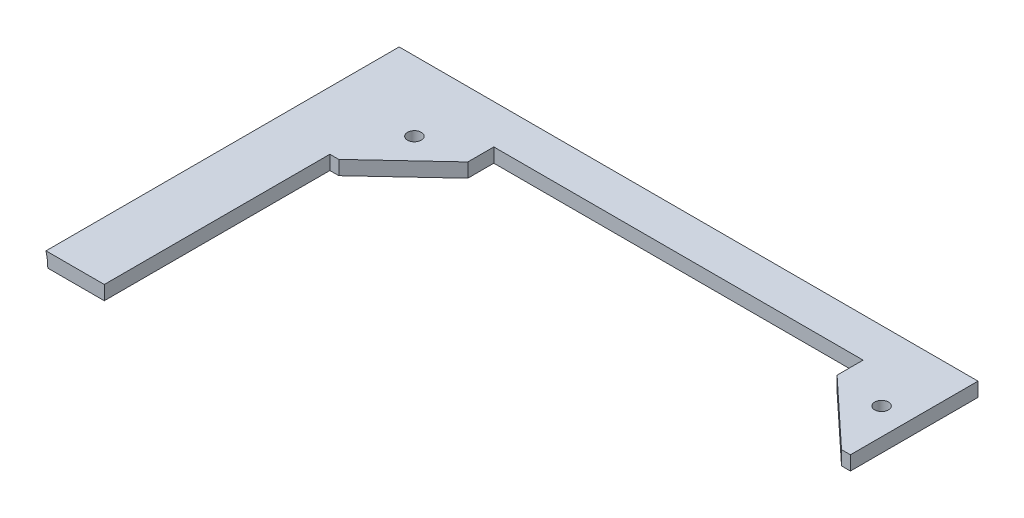
SolidWorks part; units mm, degrees
material "AISI 4130 Steel, annealed at 865C"
ref_plane "X-Y Datum" through (0, 0, 0) normal (0, 0, 1) x (1, 0, 0)
ref_plane "X-Z Datum" through (0, 0, 0) normal (0, 1, 0) x (1, 0, 0)
ref_plane "Y-Z Datum" through (0, 0, 0) normal (1, 0, 0) x (0, 0, -1)
sketch "Sketch1" plane through (0, 0, 0) normal (0, 1, 0) x (1, 0, 0)
  line L1 (-76.2, -38.1) -> (76.2, -38.1)
  line L2 (-76.2, -38.1) -> (-76.2, 38.1)
  line L3 (-76.2, 38.1) -> (76.2, 38.1)
  line L4 (76.2, -38.1) -> (76.2, 38.1)
  line L5 (-76.2, -38.1) -> (76.2, 38.1) construction
  line L6 (-76.2, 38.1) -> (76.2, -38.1) construction
  point P0 (0, 0)
  dimension "D1" = 152.4
  dimension "D2" = 76.2
extrude "Boss-Extrude1" add sketch "Sketch1" along normal blind 3.175 contours L3 L4 L1 L2
sketch "Sketch2" plane through (0, 3.175, 0) normal (0, 1, 0) x (1, 0, 0)
  line L0 (-56.5, 12.6) -> (-41.5, 26.6) construction
  line L1 (-41.5, 26.6) -> (-41.5, 32.45) construction
  line L2 (-41.5, 32.45) -> (41.5, 32.45) construction
  line L3 (41.5, 32.45) -> (41.5, 26.6) construction
  line L4 (-76.2, 38.1) -> (-76.2, -38.1)
  line L5 (-76.2, -38.1) -> (76.2, -38.1)
  line L6 (76.2, -38.1) -> (76.2, 38.1)
  line L7 (76.2, 38.1) -> (-76.2, 38.1)
  line L8 (-76.2, 38.1) -> (-76.2, -38.1)
  line L9 (-76.2, -38.1) -> (76.2, -38.1)
  line L10 (76.2, -38.1) -> (76.2, 38.1)
  line L11 (76.2, 38.1) -> (-76.2, 38.1)
  line L12 (41.5, 26.6) -> (56.5, 12.6) construction
  line L13 (-56.5, 12.6) -> (-41.5, 26.6)
  line L14 (-41.5, 26.6) -> (-41.5, 32.45)
  line L15 (-41.5, 32.45) -> (41.5, 32.45)
  line L16 (41.5, 32.45) -> (41.5, 26.6)
  line L17 (41.5, 26.6) -> (56.5, 12.6)
  line L18 (56.5, 12.6) -> (76.2, 12.6)
  line L19 (-56.5, 12.6) -> (-58.5, 12.6)
  line L20 (58.5, -451.9) -> (58.5, 38.1) construction
  line L21 (58.5, 12.6) -> (58.5, 38.1)
  line L22 (-58.5, 38.1) -> (-58.5, -451.9) construction
  line L23 (-58.5, 38.1) -> (-58.5, -38.1)
  circle A0 centre (-52.5052, 25.6052) radius 1.5453 construction
  circle A1 centre (52.5, 25.6052) radius 1.5453 construction
  circle A2 centre (-52.5052, 25.6052) radius 1.5453
  circle A3 centre (52.5, 25.6052) radius 1.5453
  line M6 (-76.2, -38.1) -> (76.2, -38.1)
  line M7 (76.2, -38.1) -> (76.2, 38.1)
  line M8 (76.2, 38.1) -> (-76.2, 38.1)
  dimension "D1" = 0
extrude "Cut-Extrude4" cut sketch "Sketch2" against normal through all contours L13 L19 L8 L18 L17 L16 L15 L14 M6 M7 | L21 L18 L10 M8 | A2 | A3 | A2 region at (6.9576, 3.175, 5.3341) region at (67.35, 3.175, -25.35) region at (-52.5052, 3.175, -25.6052) region at (52.5, 3.175, -25.6052)
sketch "Sketch3" plane through (0, 0, -38.1) normal (0, 0, -1) x (-1, 0, 0)
  line L4 (76.2, 3.175) -> (-58.5, 3.175)
  line L5 (-58.5, 3.175) -> (-58.5, 0)
  line L6 (-58.5, 0) -> (76.2, 0)
  line L7 (76.2, 0) -> (76.2, 3.175)
  line L8 (76.2, 3.175) -> (-58.5, 3.175)
  line L9 (-58.5, 3.175) -> (-58.5, 0)
  line L10 (-58.5, 0) -> (76.2, 0)
  line L11 (76.2, 0) -> (76.2, 3.175)
  dimension "D1" = 0
extrude "Boss-Extrude2" add sketch "Sketch3" along normal blind 3.175
sketch "Sketch6" plane through (0, 0, 0) normal (0, -1, 0) x (1, 0, 0)
  line L0 (58.5, -41.275) -> (-76.2, -41.275) construction
  line L1 (58.5, -41.275) -> (-76.2, -41.275) construction
  line L14 (58.5, -38.1) -> (-76.2, -38.1) construction
  dimension "D1" = 3.175
sketch "Sketch7" plane through (0, 3.175, 0) normal (0, 1, 0) x (1, 0, 0)
  line L2 (-76.2, 38.1) -> (58.5, 38.1)
  line L3 (-76.2, 38.1) -> (58.5, 38.1) construction
  dimension "D1" = 3.175
sketch3d "3DSketch6"
  line L0 (-83.9, 0, -54.0839) -> (-83.9, 0, 450.4546)
sweep "Cut-Sweep1" cut path "3DSketch6" circular profile diameter 25.4 parameters "D3"=25.4
